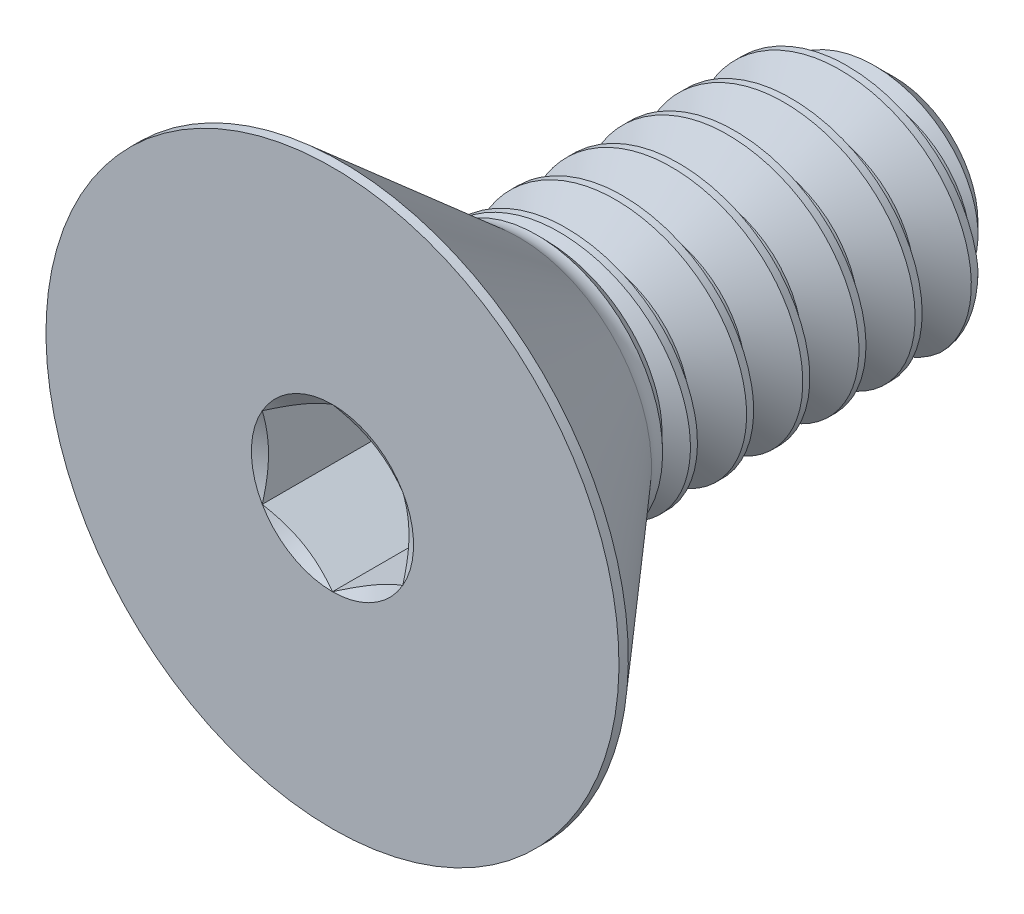
SolidWorks part; units mm, degrees
ref_plane "Front" through (0, 0, 0) normal (0, 0, 1) x (1, 0, 0)
ref_plane "Top" through (0, 0, 0) normal (0, 1, 0) x (1, 0, 0)
ref_plane "Right" through (0, 0, 0) normal (1, 0, 0) x (0, 0, -1)
sketch "Sketch1" plane through (0, 0, 0) normal (1, 0, 0) x (0, 0, -1)
  line L0 (0, 3.2385) -> (0.1054, 3.2385) construction
  line L1 (0.1054, 3.2385) -> (2.1082, 1.4975) construction
  line L2 (0, 1.4224) -> (6.35, 1.4224)
  line L3 (6.35, 1.4224) -> (6.35, 0)
  line L4 (6.35, 0) -> (0, 0)
  line L5 (0, 0) -> (0, 3.2385) construction
  line L6 (0, 3.2385) -> (0, -3.2385) construction
  line L7 (6.35, 1.4224) -> (6.35, -1.4224) construction
  line L8 (0, -3.2385) -> (0.1054, -3.2385) construction
  line L9 (0.1054, -3.2385) -> (2.1082, -1.4975) construction
  line L11 (0, 1.4224) -> (0, 0)
  line L12 (2.3091, 1.4224) -> (2.3091, 0) construction
  line L13 (-19.05, 0) -> (-19.05, 1.4224) construction
  arc A1 (2.1082, 1.4975) -> (2.3091, 1.4224) centre (2.3091, 1.7286) ccw construction
  dimension "D1" = 0.1054
  dimension "Min Thread" = 25.4
revolve "Revolve1" add sketch "Sketch1" angle 360 mid plane about L4
sketch "Sketch3" plane through (0, 0, -6.35) normal (0, 0, -1) x (-1, 0, 0)
  circle A0 centre (0, 0) radius 1.4224
curve "Helix/Spiral1" pitch 0.635 height 6.35 radius 1.4224 centre (0, 0, -6.35) axis (0, 0, 1) start towards (0, 1, 0)
sketch "Sketch2" plane through (0, 0, 0) normal (1, 0, 0) x (0, 0, -1)
  line L0 (6.35, 1.4224) -> (6.9056, 1.4224)
  line L1 (6.9056, 1.4224) -> (6.6675, 1.01)
  line L2 (6.6675, 1.01) -> (6.5881, 1.01)
  line L3 (6.5881, 1.01) -> (6.35, 1.4224)
  line L4 (6.4691, 1.2162) -> (6.7866, 1.2162) construction
  dimension "D1" = 60
  dimension "D2" = 0.0794
  dimension "D3" = 0.3175
ref_plane "Plane2" through (0, 0, 19.05) normal (0, 0, 1) x (1, 0, 0)
chamfer "Chamfer1" distance 0.4763 angle 45 1 edges at (0, 1.4224, -6.35)
sweep "Cut-Sweep1" cut profiles "Sketch2" path "Helix/Spiral1" align with end faces yes
sketch "Sketch7" plane through (0, 0, 0) normal (1, 0, 0) x (0, 0, -1)
  line L0 (0, 3.2385) -> (0.1054, 3.2385) construction
  line L1 (0.1054, 3.2385) -> (2.1082, 1.4975) construction
  line L2 (0, 3.2385) -> (0.1054, 3.2385)
  line L3 (0.1054, 3.2385) -> (2.1082, 1.4975)
  line L4 (2.3091, 1.4224) -> (2.3091, 0) construction
  line L5 (2.3091, 1.4224) -> (2.3091, 0)
  line L7 (0, 0) -> (0, 3.2385) construction
  line L8 (0, 0) -> (0, 3.2385)
  line L9 (0, 0) -> (2.3091, 0)
  line L10 (5.7417, 0) -> (-5.7417, 0) construction
  arc A0 (2.1082, 1.4975) -> (2.3091, 1.4224) centre (2.3091, 1.7286) ccw construction
  arc A1 (2.1082, 1.4975) -> (2.3091, 1.4224) centre (2.3091, 1.7286) ccw
revolve "Revolve2" add sketch "Sketch7" angle 360 mid plane about L9
ref_plane "Plane1" through (0, 0, -2.3091) normal (0, 0, 1) x (1, 0, 0)
sketch "Sketch8" plane through (0, 0, -2.3091) normal (0, 0, 1) x (1, 0, 0)
  circle A0 centre (0, 0) radius 1.4224
extrude "Boss-Extrude1" add sketch "Sketch8" against normal through all draft 46
sketch "Sketch5" plane through (0, 0, 0) normal (0, 0, 1) x (1, 0, 0)
  line L0 (0, 0) -> (-0.9165, 0) construction
  line L1 (0, 0) -> (-2.7496, 1.5875) construction
  line L2 (0, 0) -> (-2.7496, -1.5875) construction
  line L6 (0, 0.9165) -> (0, 0.7559) construction
  line L7 (0, 0.7559) -> (0, 0.5953) construction
  line L9 (0, 0.9165) -> (-0.7937, 0.4583)
  line L10 (-0.7937, 0.4583) -> (-0.7937, -0.4583)
  line L11 (-0.7937, -0.4583) -> (0, -0.9165)
  line L12 (0, -0.9165) -> (0.7937, -0.4583)
  line L13 (0.7937, -0.4583) -> (0.7938, 0.4583)
  line L14 (0.7938, 0.4583) -> (0, 0.9165)
  circle A0 centre (0, 0) radius 0.9165 construction
  circle A1 centre (0, 0) radius 0.7559 construction
  circle A2 centre (0, 0) radius 0.5953 construction
  circle A3 centre (0, 0) radius 0.7938 construction
  dimension "D3" = 1.1906
  dimension "D4" = 30
  dimension "D5" = 30
  dimension "Hex" = 1.5875
extrude "Cut-Extrude2" cut sketch "Sketch5" against normal blind 1.4757
sketch "Sketch6" plane through (0, 0, 0) normal (0, 0, 1) x (1, 0, 0)
  circle A0 centre (0, 0) radius 0.9165
extrude "Cut-Extrude3" cut sketch "Sketch6" against normal blind 1.4757 draft 60
sketch "Sketch9" [suppressed] plane through (0, 0, -3.6076) normal (0, 0, 1) x (1, 0, 0)
  circle A1 centre (0, 0) radius 2.413
  circle A2 centre (0, 0) radius 2.413
  point P0 (0, 2.413)
  dimension "D1" = 0
extrude "Boss-Extrude2" [suppressed] add sketch "Sketch9" against normal up to surface (15.4424 mm away) up to plane "Plane2"
sketch "Sketch10" plane through (0, 0, 0) normal (1, 0, 0) x (0, 0, -1)
  line L0 (6.35, 1.4224) -> (6.35, -1.4224) construction
  point P0 (5.3975, -1.4224)
  dimension "D1" = 0.9525
equation "\"D3@Helix/Spiral1\" = \"Lg@Sketch1\""
equation "\"D2@Sketch2\" = \"D4@Helix/Spiral1\" * .125"
equation "\"D3@Sketch2\" = \"D4@Helix/Spiral1\" * .5"
equation "\"D1@Chamfer1\" = \"D4@Helix/Spiral1\" * .75"
equation "\"D1@Cut-Extrude2\" = \"Head Ht@Sketch1\" * .7"
equation "\"D1@Sketch1\" = \"Head Ht@Sketch1\" * .05"
equation "\"D1@Sketch10\" = \"D4@Helix/Spiral1\" * 1.5"
equation "\"D1@Cut-Extrude3\" = \"D1@Cut-Extrude2\""
equation "\"D3@Sketch5\" = \"Hex@Sketch5\" * .75"
